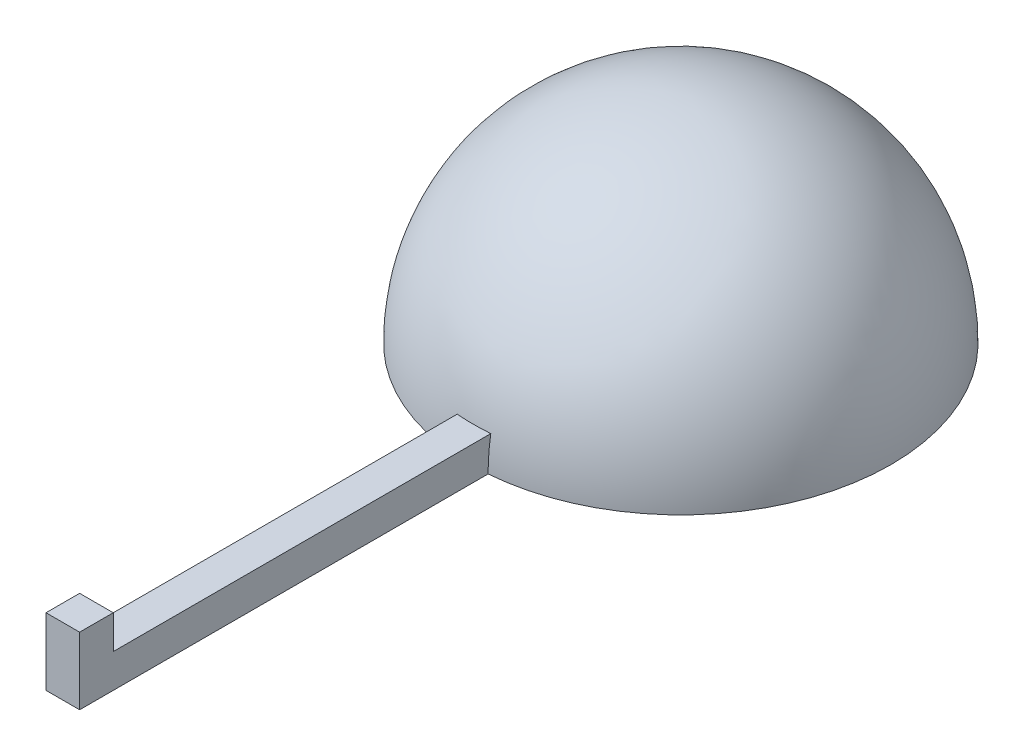
SolidWorks part; units mm, degrees
ref_plane "Front Plane" through (0, 0, 0) normal (0, 0, 1) x (1, 0, 0)
ref_plane "Top Plane" through (0, 0, 0) normal (0, 1, 0) x (1, 0, 0)
ref_plane "Right Plane" through (0, 0, 0) normal (1, 0, 0) x (0, 0, -1)
sketch "Sketch1" plane through (0, 0, 0) normal (0, 1, 0) x (1, 0, 0)
  line L0 (-50, 0) -> (50, 0)
  arc A0 (-50, 0) -> (50, 0) centre (0, 0) cw
  dimension "D1" = 50
revolve "Revolve1" add sketch "Sketch1" angle 180 about L0
shell "Shell3" thickness 3 removed face at (0, 0, 50)
sketch "Sketch5" plane through (0, 0, 0) normal (1, 0, 0) x (0, 0, -1)
  line L0 (-47, 0) -> (-47, 8)
  line L1 (-47, 8) -> (-139, 8)
  line L2 (-139, 8) -> (-139, 16)
  line L3 (-139, 16) -> (-147, 16)
  line L4 (-147, 16) -> (-147, 0)
  line L5 (-147, 0) -> (-47, 0)
  dimension "D1" = 100
  dimension "D2" = 8
  dimension "D3" = 8
  dimension "D4" = 8
extrude "Boss-Extrude1" add sketch "Sketch5" along normal mid plane 8
equation "\"D4@Sketch5\"=\"D2@Sketch5\""
equation "\"D3@Sketch5\"=\"D2@Sketch5\""
